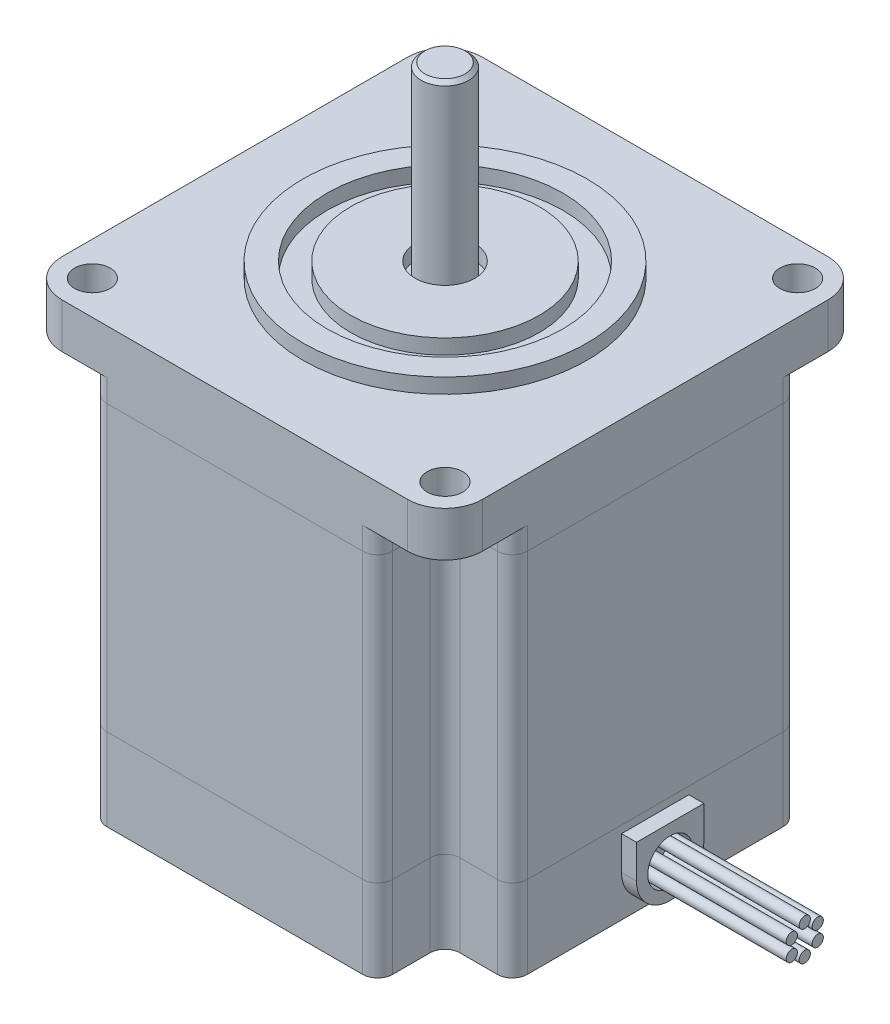
SolidWorks part; units mm, degrees
other "Camera1"
ref_plane "Front Plane" through (0, 0, 0) normal (0, 0, 1) x (1, 0, 0)
ref_plane "Top Plane" through (0, 0, 0) normal (0, 1, 0) x (1, 0, 0)
ref_plane "Right Plane" through (0, 0, 0) normal (1, 0, 0) x (0, 0, -1)
sketch "Sketch1" plane through (0, 0, 0) normal (0, 1, 0) x (1, 0, 0)
  line L1 (28.1, -28.1) -> (-28.1, -28.1)
  line L2 (28.1, -28.1) -> (28.1, 28.1)
  line L3 (28.1, 28.1) -> (-28.1, 28.1)
  line L4 (-28.1, -28.1) -> (-28.1, 28.1)
  line L5 (0, 28.1) -> (0, -28.1) construction
  line L6 (21, 0) -> (-28.1, 0) construction
  circle A0 centre (23.57, 23.57) radius 2.375
  circle A1 centre (23.57, -23.57) radius 2.375
  circle A2 centre (-23.57, -23.57) radius 2.375
  circle A3 centre (-23.57, 23.57) radius 2.375
  point P0 (0, 0)
  point P1 (-28.1, 28.1)
  point P6 (0, 28.1)
  point P7 (-28.1, 0)
  point P15 (0, 0)
  point P19 (0, -28.1)
  dimension "D2" = 4.75
  dimension "D1" = 56.2
  dimension "D4" = 47.14
  dimension "D3" = 4
extrude "Boss-Extrude2" add sketch "Sketch1" along normal blind 11
sketch "Sketch2" plane through (0, 11, 0) normal (0, 1, 0) x (1, 0, 0)
  line L8 (28.1, 28.1) -> (-28.1, 28.1)
  line L10 (-28.1, 28.1) -> (-28.1, -28.1)
  line L12 (-28.1, -28.1) -> (28.1, -28.1)
  line L14 (28.1, -28.1) -> (28.1, 28.1)
  line L16 (28.1, 28.1) -> (-28.1, 28.1)
  line L18 (-28.1, 28.1) -> (-28.1, -28.1)
  line L20 (-28.1, -28.1) -> (28.1, -28.1)
  line L22 (28.1, -28.1) -> (28.1, 28.1)
  circle A0 centre (-23.57, -23.57) radius 2.375 construction
  circle A1 centre (23.57, -23.57) radius 2.375 construction
  circle A2 centre (23.57, 23.57) radius 2.375 construction
  circle A3 centre (-23.57, 23.57) radius 2.375 construction
  circle A4 centre (-23.57, -23.57) radius 2.375
  circle A5 centre (23.57, -23.57) radius 2.375
  circle A6 centre (23.57, 23.57) radius 2.375
  circle A7 centre (-23.57, 23.57) radius 2.375
  dimension "D1" = 0
extrude "Boss-Extrude3" add sketch "Sketch2" along normal blind 38 separate body
sketch "Sketch3" plane through (0, 49, 0) normal (0, 1, 0) x (1, 0, 0)
  line L9 (28.1, 28.1) -> (-28.1, 28.1)
  line L11 (-28.1, 28.1) -> (-28.1, -28.1)
  line L13 (-28.1, -28.1) -> (28.1, -28.1)
  line L15 (28.1, -28.1) -> (28.1, 28.1)
  line L17 (28.1, 28.1) -> (-28.1, 28.1)
  line L19 (-28.1, 28.1) -> (-28.1, -28.1)
  line L21 (-28.1, -28.1) -> (28.1, -28.1)
  line L23 (28.1, -28.1) -> (28.1, 28.1)
  circle A0 centre (23.57, 23.57) radius 2.375 construction
  circle A1 centre (23.57, -23.57) radius 2.375 construction
  circle A2 centre (-23.57, -23.57) radius 2.375 construction
  circle A3 centre (-23.57, 23.57) radius 2.375 construction
  circle A4 centre (23.57, 23.57) radius 2.375
  circle A5 centre (23.57, -23.57) radius 2.375
  circle A6 centre (-23.57, -23.57) radius 2.375
  circle A7 centre (-23.57, 23.57) radius 2.375
  dimension "D1" = 0
extrude "Boss-Extrude4" add sketch "Sketch3" along normal blind 9 separate body
sketch "Sketch4" plane through (28.1, 0, 0) normal (1, 0, 0) x (0, 0, -1)
  line L1 (0, 0) -> (0, 11) construction
  line L2 (-28.1, 11) -> (28.1, 11) construction
  line L3 (-4.5, 5.5) -> (-4.5, 10)
  line L4 (-4.5, 10) -> (4.5, 10)
  line L5 (4.5, 5.5) -> (4.5, 10)
  arc A0 (-4.5, 5.5) -> (4.5, 5.5) centre (0, 5.5) ccw
  circle A1 centre (0, 5.5) radius 3
  point P11 (0, 10)
  dimension "D1" = 6
  dimension "D2" = 9
extrude "Boss-Extrude5" add sketch "Sketch4" along normal blind 2 separate body
sketch "Sketch5" plane through (28.1, 0, 0) normal (1, 0, 0) x (0, 0, -1)
  circle A0 centre (-1.7321, 4.5) radius 0.75
  circle A1 centre (0, 3.5) radius 0.75
  circle A2 centre (-1.7321, 6.5) radius 0.75
  circle A3 centre (0, 7.5) radius 0.75
  circle A4 centre (1.7321, 6.5) radius 0.75
  circle A5 centre (1.7321, 4.5) radius 0.75
  circle A6 centre (0, 5.5) radius 2 construction
  point P15 (0, 5.5)
  dimension "D1" = 1.5
  dimension "D3" = 4
  dimension "D2" = 6
extrude "Boss-Extrude6" add sketch "Sketch5" along normal blind 20 separate body contours A2 | A0 | A1 | A5 | A4 | A3
sketch "Sketch6" plane through (0, 58, 0) normal (0, 1, 0) x (1, 0, 0)
  circle A0 centre (0, 0) radius 12.6
  circle A1 centre (0, 0) radius 19
  circle A2 centre (0, 0) radius 15.75
  circle A3 centre (0, 0) radius 4
  dimension "D1" = 25.2
  dimension "D2" = 38
  dimension "D3" = 31.5
  dimension "D4" = 8
extrude "Boss-Extrude7" add sketch "Sketch6" along normal blind 2 contours A1 A2 | A0 region at (-12.2436, 58, 0) region at (-18.4626, 58, 0)
sketch "Sketch7" plane through (0, 58, 0) normal (0, 1, 0) x (1, 0, 0)
  circle A0 centre (0, 0) radius 3.175
  dimension "D1" = 6.35
extrude "Boss-Extrude8" add sketch "Sketch7" along normal blind 25 separate body
sketch "Sketch8" plane through (0, 83, 0) normal (0, 1, 0) x (1, 0, 0)
  circle A0 centre (0, 0) radius 7.675
  circle A1 centre (0, 0) radius 3.175
  circle A2 centre (0, 0) radius 3.175
  dimension "D2" = 15.35
  dimension "D1" = 0
extrude "Boss-Extrude9" [suppressed] add sketch "Sketch8" against normal blind 10 separate body
sketch "Sketch9" [suppressed] plane through (0, 56, 0) normal (0, -1, 0) x (1, 0, 0)
  circle A0 centre (0, 0) radius 10
  dimension "D1" = 20
extrude "Boss-Extrude10" [suppressed] add sketch "Sketch9" against normal blind 1
sketch "Sketch10" [suppressed] plane through (0, 66, 0) normal (0, 1, 0) x (1, 0, 0)
  line L0 (0, 7.675) -> (0, 8.675) construction
  line L1 (-0.6, 7.6515) -> (-0.3, 8.4658)
  line L2 (0.6, 7.6515) -> (0.3, 8.4658)
  line L3 (1.1177, 7.5932) -> (1.5913, 8.3203)
  line L4 (2.2876, 7.3262) -> (2.1763, 8.1868)
  line L5 (1.7078, 7.4826) -> (1.9304, 8.4575) construction
  line L6 (2.7793, 7.1541) -> (3.4029, 7.7576)
  line L7 (3.8604, 6.6334) -> (3.9435, 7.4973)
  line L8 (3.3301, 6.9149) -> (3.7639, 7.8159) construction
  line L9 (4.3015, 6.3563) -> (5.0438, 6.8059)
  line L10 (5.2397, 5.6081) -> (5.5129, 6.4318)
  line L11 (4.7853, 6.0006) -> (5.4088, 6.7824) construction
  line L12 (5.6081, 5.2397) -> (6.4318, 5.5129)
  line L13 (6.3563, 4.3015) -> (6.8059, 5.0438)
  line L14 (6.0006, 4.7853) -> (6.7824, 5.4088) construction
  line L15 (6.6334, 3.8604) -> (7.4973, 3.9435)
  line L16 (7.1541, 2.7793) -> (7.7576, 3.4029)
  line L17 (6.9149, 3.3301) -> (7.8159, 3.7639) construction
  line L18 (7.3262, 2.2876) -> (8.1868, 2.1763)
  line L19 (7.5932, 1.1177) -> (8.3203, 1.5913)
  line L20 (7.4826, 1.7078) -> (8.4575, 1.9304) construction
  line L21 (7.6515, 0.6) -> (8.4658, 0.3)
  line L22 (7.6515, -0.6) -> (8.4658, -0.3)
  line L23 (7.675, 0) -> (8.675, 0) construction
  line L24 (7.5932, -1.1177) -> (8.3203, -1.5913)
  line L25 (7.3262, -2.2876) -> (8.1868, -2.1763)
  line L26 (7.4826, -1.7078) -> (8.4575, -1.9304) construction
  line L27 (7.1541, -2.7793) -> (7.7576, -3.4029)
  line L28 (6.6334, -3.8604) -> (7.4973, -3.9435)
  line L29 (6.9149, -3.3301) -> (7.8159, -3.7639) construction
  line L30 (6.3563, -4.3015) -> (6.8059, -5.0438)
  line L31 (5.6081, -5.2397) -> (6.4318, -5.5129)
  line L32 (6.0006, -4.7853) -> (6.7824, -5.4088) construction
  line L33 (5.2397, -5.6081) -> (5.5129, -6.4318)
  line L34 (4.3015, -6.3563) -> (5.0438, -6.8059)
  line L35 (4.7853, -6.0006) -> (5.4088, -6.7824) construction
  line L36 (3.8604, -6.6334) -> (3.9435, -7.4973)
  line L37 (2.7793, -7.1541) -> (3.4029, -7.7576)
  line L38 (3.3301, -6.9149) -> (3.7639, -7.8159) construction
  line L39 (2.2876, -7.3262) -> (2.1763, -8.1868)
  line L40 (1.1177, -7.5932) -> (1.5913, -8.3203)
  line L41 (1.7078, -7.4826) -> (1.9304, -8.4575) construction
  line L42 (0.6, -7.6515) -> (0.3, -8.4658)
  line L43 (-0.6, -7.6515) -> (-0.3, -8.4658)
  line L44 (0, -7.675) -> (0, -8.675) construction
  line L45 (-1.1177, -7.5932) -> (-1.5913, -8.3203)
  line L46 (-2.2876, -7.3262) -> (-2.1763, -8.1868)
  line L47 (-1.7078, -7.4826) -> (-1.9304, -8.4575) construction
  line L48 (-2.7793, -7.1541) -> (-3.4029, -7.7576)
  line L49 (-3.8604, -6.6334) -> (-3.9435, -7.4973)
  line L50 (-3.3301, -6.9149) -> (-3.7639, -7.8159) construction
  line L51 (-4.3015, -6.3563) -> (-5.0438, -6.8059)
  line L52 (-5.2397, -5.6081) -> (-5.5129, -6.4318)
  line L53 (-4.7853, -6.0006) -> (-5.4088, -6.7824) construction
  line L54 (-5.6081, -5.2397) -> (-6.4318, -5.5129)
  line L55 (-6.3563, -4.3015) -> (-6.8059, -5.0438)
  line L56 (-6.0006, -4.7853) -> (-6.7824, -5.4088) construction
  line L57 (-6.6334, -3.8604) -> (-7.4973, -3.9435)
  line L58 (-7.1541, -2.7793) -> (-7.7576, -3.4029)
  line L59 (-6.9149, -3.3301) -> (-7.8159, -3.7639) construction
  line L60 (-7.3262, -2.2876) -> (-8.1868, -2.1763)
  line L61 (-7.5932, -1.1177) -> (-8.3203, -1.5913)
  line L62 (-7.4826, -1.7078) -> (-8.4575, -1.9304) construction
  line L63 (-7.6515, -0.6) -> (-8.4658, -0.3)
  line L64 (-7.6515, 0.6) -> (-8.4658, 0.3)
  line L65 (-7.675, 0) -> (-8.675, 0) construction
  line L66 (-7.5932, 1.1177) -> (-8.3203, 1.5913)
  line L67 (-7.3262, 2.2876) -> (-8.1868, 2.1763)
  line L68 (-7.4826, 1.7078) -> (-8.4575, 1.9304) construction
  line L69 (-7.1541, 2.7793) -> (-7.7576, 3.4029)
  line L70 (-6.6334, 3.8604) -> (-7.4973, 3.9435)
  line L71 (-6.9149, 3.3301) -> (-7.8159, 3.7639) construction
  line L72 (-6.3563, 4.3015) -> (-6.8059, 5.0438)
  line L73 (-5.6081, 5.2397) -> (-6.4318, 5.5129)
  line L74 (-6.0006, 4.7853) -> (-6.7824, 5.4088) construction
  line L75 (-5.2397, 5.6081) -> (-5.5129, 6.4318)
  line L76 (-4.3015, 6.3563) -> (-5.0438, 6.8059)
  line L77 (-4.7853, 6.0006) -> (-5.4088, 6.7824) construction
  line L78 (-3.8604, 6.6334) -> (-3.9435, 7.4973)
  line L79 (-2.7793, 7.1541) -> (-3.4029, 7.7576)
  line L80 (-3.3301, 6.9149) -> (-3.7639, 7.8159) construction
  line L81 (-2.2876, 7.3262) -> (-2.1763, 8.1868)
  line L82 (-1.1177, 7.5932) -> (-1.5913, 8.3203)
  line L83 (-1.7078, 7.4826) -> (-1.9304, 8.4575) construction
  circle A0 centre (0, 0) radius 8.675 construction
  circle A1 centre (0, 0) radius 7.675 construction
  circle A2 centre (0, 0) radius 7.675 construction
  arc A3 (-0.3, 8.4658) -> (0, 8.675) centre (0, 8.3553) cw
  circle A4 centre (0, 0) radius 7.675
  arc A5 (0.6, 7.6515) -> (-0.6, 7.6515) centre (0, 0) ccw
  arc A6 (0.3, 8.4658) -> (0, 8.675) centre (0, 8.3553) ccw
  arc A7 (1.5913, 8.3203) -> (1.9304, 8.4575) centre (1.8592, 8.1458) cw
  arc A8 (2.2876, 7.3262) -> (1.1177, 7.5932) centre (0, 0) ccw
  arc A9 (2.1763, 8.1868) -> (1.9304, 8.4575) centre (1.8592, 8.1458) ccw
  arc A10 (3.4029, 7.7576) -> (3.7639, 7.8159) centre (3.6252, 7.5279) cw
  arc A11 (3.8604, 6.6334) -> (2.7793, 7.1541) centre (0, 0) ccw
  arc A12 (3.9435, 7.4973) -> (3.7639, 7.8159) centre (3.6252, 7.5279) ccw
  arc A13 (5.0438, 6.8059) -> (5.4088, 6.7824) centre (5.2094, 6.5324) cw
  arc A14 (5.2397, 5.6081) -> (4.3015, 6.3563) centre (0, 0) ccw
  arc A15 (5.5129, 6.4318) -> (5.4088, 6.7824) centre (5.2094, 6.5324) ccw
  arc A16 (6.4318, 5.5129) -> (6.7824, 5.4088) centre (6.5324, 5.2094) cw
  arc A17 (6.3563, 4.3015) -> (5.6081, 5.2397) centre (0, 0) ccw
  arc A18 (6.8059, 5.0438) -> (6.7824, 5.4088) centre (6.5324, 5.2094) ccw
  arc A19 (7.4973, 3.9435) -> (7.8159, 3.7639) centre (7.5279, 3.6252) cw
  arc A20 (7.1541, 2.7793) -> (6.6334, 3.8604) centre (0, 0) ccw
  arc A21 (7.7576, 3.4029) -> (7.8159, 3.7639) centre (7.5279, 3.6252) ccw
  arc A22 (8.1868, 2.1763) -> (8.4575, 1.9304) centre (8.1458, 1.8592) cw
  arc A23 (7.5932, 1.1177) -> (7.3262, 2.2876) centre (0, 0) ccw
  arc A24 (8.3203, 1.5913) -> (8.4575, 1.9304) centre (8.1458, 1.8592) ccw
  arc A25 (8.4658, 0.3) -> (8.675, 0) centre (8.3553, 0) cw
  arc A26 (7.6515, -0.6) -> (7.6515, 0.6) centre (0, 0) ccw
  arc A27 (8.4658, -0.3) -> (8.675, 0) centre (8.3553, 0) ccw
  arc A28 (8.3203, -1.5913) -> (8.4575, -1.9304) centre (8.1458, -1.8592) cw
  arc A29 (7.3262, -2.2876) -> (7.5932, -1.1177) centre (0, 0) ccw
  arc A30 (8.1868, -2.1763) -> (8.4575, -1.9304) centre (8.1458, -1.8592) ccw
  arc A31 (7.7576, -3.4029) -> (7.8159, -3.7639) centre (7.5279, -3.6252) cw
  arc A32 (6.6334, -3.8604) -> (7.1541, -2.7793) centre (0, 0) ccw
  arc A33 (7.4973, -3.9435) -> (7.8159, -3.7639) centre (7.5279, -3.6252) ccw
  arc A34 (6.8059, -5.0438) -> (6.7824, -5.4088) centre (6.5324, -5.2094) cw
  arc A35 (5.6081, -5.2397) -> (6.3563, -4.3015) centre (0, 0) ccw
  arc A36 (6.4318, -5.5129) -> (6.7824, -5.4088) centre (6.5324, -5.2094) ccw
  arc A37 (5.5129, -6.4318) -> (5.4088, -6.7824) centre (5.2094, -6.5324) cw
  arc A38 (4.3015, -6.3563) -> (5.2397, -5.6081) centre (0, 0) ccw
  arc A39 (5.0438, -6.8059) -> (5.4088, -6.7824) centre (5.2094, -6.5324) ccw
  arc A40 (3.9435, -7.4973) -> (3.7639, -7.8159) centre (3.6252, -7.5279) cw
  arc A41 (2.7793, -7.1541) -> (3.8604, -6.6334) centre (0, 0) ccw
  arc A42 (3.4029, -7.7576) -> (3.7639, -7.8159) centre (3.6252, -7.5279) ccw
  arc A43 (2.1763, -8.1868) -> (1.9304, -8.4575) centre (1.8592, -8.1458) cw
  arc A44 (1.1177, -7.5932) -> (2.2876, -7.3262) centre (0, 0) ccw
  arc A45 (1.5913, -8.3203) -> (1.9304, -8.4575) centre (1.8592, -8.1458) ccw
  arc A46 (0.3, -8.4658) -> (0, -8.675) centre (0, -8.3553) cw
  arc A47 (-0.6, -7.6515) -> (0.6, -7.6515) centre (0, 0) ccw
  arc A48 (-0.3, -8.4658) -> (0, -8.675) centre (0, -8.3553) ccw
  arc A49 (-1.5913, -8.3203) -> (-1.9304, -8.4575) centre (-1.8592, -8.1458) cw
  arc A50 (-2.2876, -7.3262) -> (-1.1177, -7.5932) centre (0, 0) ccw
  arc A51 (-2.1763, -8.1868) -> (-1.9304, -8.4575) centre (-1.8592, -8.1458) ccw
  arc A52 (-3.4029, -7.7576) -> (-3.7639, -7.8159) centre (-3.6252, -7.5279) cw
  arc A53 (-3.8604, -6.6334) -> (-2.7793, -7.1541) centre (0, 0) ccw
  arc A54 (-3.9435, -7.4973) -> (-3.7639, -7.8159) centre (-3.6252, -7.5279) ccw
  arc A55 (-5.0438, -6.8059) -> (-5.4088, -6.7824) centre (-5.2094, -6.5324) cw
  arc A56 (-5.2397, -5.6081) -> (-4.3015, -6.3563) centre (0, 0) ccw
  arc A57 (-5.5129, -6.4318) -> (-5.4088, -6.7824) centre (-5.2094, -6.5324) ccw
  arc A58 (-6.4318, -5.5129) -> (-6.7824, -5.4088) centre (-6.5324, -5.2094) cw
  arc A59 (-6.3563, -4.3015) -> (-5.6081, -5.2397) centre (0, 0) ccw
  arc A60 (-6.8059, -5.0438) -> (-6.7824, -5.4088) centre (-6.5324, -5.2094) ccw
  arc A61 (-7.4973, -3.9435) -> (-7.8159, -3.7639) centre (-7.5279, -3.6252) cw
  arc A62 (-7.1541, -2.7793) -> (-6.6334, -3.8604) centre (0, 0) ccw
  arc A63 (-7.7576, -3.4029) -> (-7.8159, -3.7639) centre (-7.5279, -3.6252) ccw
  arc A64 (-8.1868, -2.1763) -> (-8.4575, -1.9304) centre (-8.1458, -1.8592) cw
  arc A65 (-7.5932, -1.1177) -> (-7.3262, -2.2876) centre (0, 0) ccw
  arc A66 (-8.3203, -1.5913) -> (-8.4575, -1.9304) centre (-8.1458, -1.8592) ccw
  arc A67 (-8.4658, -0.3) -> (-8.675, 0) centre (-8.3553, 0) cw
  arc A68 (-7.6515, 0.6) -> (-7.6515, -0.6) centre (0, 0) ccw
  arc A69 (-8.4658, 0.3) -> (-8.675, 0) centre (-8.3553, 0) ccw
  arc A70 (-8.3203, 1.5913) -> (-8.4575, 1.9304) centre (-8.1458, 1.8592) cw
  arc A71 (-7.3262, 2.2876) -> (-7.5932, 1.1177) centre (0, 0) ccw
  arc A72 (-8.1868, 2.1763) -> (-8.4575, 1.9304) centre (-8.1458, 1.8592) ccw
  arc A73 (-7.7576, 3.4029) -> (-7.8159, 3.7639) centre (-7.5279, 3.6252) cw
  arc A74 (-6.6334, 3.8604) -> (-7.1541, 2.7793) centre (0, 0) ccw
  arc A75 (-7.4973, 3.9435) -> (-7.8159, 3.7639) centre (-7.5279, 3.6252) ccw
  arc A76 (-6.8059, 5.0438) -> (-6.7824, 5.4088) centre (-6.5324, 5.2094) cw
  arc A77 (-5.6081, 5.2397) -> (-6.3563, 4.3015) centre (0, 0) ccw
  arc A78 (-6.4318, 5.5129) -> (-6.7824, 5.4088) centre (-6.5324, 5.2094) ccw
  arc A79 (-5.5129, 6.4318) -> (-5.4088, 6.7824) centre (-5.2094, 6.5324) cw
  arc A80 (-4.3015, 6.3563) -> (-5.2397, 5.6081) centre (0, 0) ccw
  arc A81 (-5.0438, 6.8059) -> (-5.4088, 6.7824) centre (-5.2094, 6.5324) ccw
  arc A82 (-3.9435, 7.4973) -> (-3.7639, 7.8159) centre (-3.6252, 7.5279) cw
  arc A83 (-2.7793, 7.1541) -> (-3.8604, 6.6334) centre (0, 0) ccw
  arc A84 (-3.4029, 7.7576) -> (-3.7639, 7.8159) centre (-3.6252, 7.5279) ccw
  arc A85 (-2.1763, 8.1868) -> (-1.9304, 8.4575) centre (-1.8592, 8.1458) cw
  arc A86 (-1.1177, 7.5932) -> (-2.2876, 7.3262) centre (0, 0) ccw
  arc A87 (-1.5913, 8.3203) -> (-1.9304, 8.4575) centre (-1.8592, 8.1458) ccw
  point P236 (0, 0)
  dimension "D1" = 17.35
  dimension "D2" = 0
  dimension "D3" = 1.2
  dimension "D5" = 0.6
  dimension "D4" = 28
extrude "Boss-Extrude12" [suppressed] add sketch "Sketch10" against normal blind 9
sketch "Sketch11" plane through (0, 0, 0) normal (0, -1, 0) x (1, 0, 0)
  line L0 (0, 21.8817) -> (0, 0) construction
  line L2 (0, 0) -> (43.9252, 0) construction
  line L4 (28.1, 23.6) -> (19.1, 23.6) construction
  line L5 (-28.1, 28.1) -> (-19.1, 28.1)
  line L6 (-28.1, 28.1) -> (-28.1, 19.1)
  line L7 (-28.1, 19.1) -> (-19.1, 19.1)
  line L8 (-19.1, 28.1) -> (-19.1, 19.1)
  line L9 (-23.6, 19.1) -> (-23.6, 28.1) construction
  line L10 (-28.1, 23.6) -> (-19.1, 23.6) construction
  line L11 (23.6, 19.1) -> (23.6, 28.1) construction
  line L12 (19.1, 28.1) -> (19.1, 19.1)
  line L13 (28.1, 19.1) -> (19.1, 19.1)
  line L14 (28.1, 28.1) -> (28.1, 19.1)
  line L15 (28.1, 28.1) -> (19.1, 28.1)
  line L16 (23.6, -19.1) -> (23.6, -28.1) construction
  line L17 (-28.1, -23.6) -> (-19.1, -23.6) construction
  line L18 (-23.6, -19.1) -> (-23.6, -28.1) construction
  line L19 (28.1, -23.6) -> (19.1, -23.6) construction
  line L20 (28.1, -28.1) -> (19.1, -28.1)
  line L21 (28.1, -28.1) -> (28.1, -19.1)
  line L22 (28.1, -19.1) -> (19.1, -19.1)
  line L23 (19.1, -28.1) -> (19.1, -19.1)
  line L24 (-19.1, -28.1) -> (-19.1, -19.1)
  line L25 (-28.1, -19.1) -> (-19.1, -19.1)
  line L26 (-28.1, -28.1) -> (-28.1, -19.1)
  line L27 (-28.1, -28.1) -> (-19.1, -28.1)
  point P20 (23.6, 23.6)
  point P38 (-23.6, -23.6)
  point P39 (23.6, -23.6)
  point P52 (-23.6, 23.6)
  dimension "D1" = 9
extrude "Cut-Extrude1" cut sketch "Sketch11" against normal offset from surface (52 mm away) 6 up to face at (0, 58, 19)
fillet "Fillet1" radius 5 4 edges at (-28.1, 55, 28.1) (28.1, 55, 28.1) (28.1, 55, -28.1) (-28.1, 55, -28.1)
fillet "Fillet2" radius 2 12 edges at (19.1, 5.5, -28.1) (19.1, 5.5, -19.1) (28.1, 5.5, -19.1) (-28.1, 5.5, -19.1) (-19.1, 5.5, -19.1) (-19.1, 5.5, -28.1) (-28.1, 5.5, 19.1) (-19.1, 5.5, 19.1) (-19.1, 5.5, 28.1) (28.1, 5.5, 19.1) (19.1, 5.5, 28.1) (19.1, 5.5, 19.1)
fillet "Fillet3" radius 2 12 edges at (28.1, 30, 19.1) (19.1, 30, 19.1) (19.1, 30, 28.1) (-19.1, 30, 28.1) (-19.1, 30, 19.1) (-28.1, 30, 19.1) (-28.1, 30, -19.1) (-19.1, 30, -19.1) (-19.1, 30, -28.1) (19.1, 30, -28.1) (28.1, 30, -19.1) (19.1, 30, -19.1)
chamfer "Chamfer1" distance 0.5 angle 45 1 edges at (0, 83, 3.175)
fillet "Fillet4" radius 2 12 edges at (19.1, 50.5, -28.1) (28.1, 50.5, -19.1) (19.1, 50.5, -19.1) (-19.1, 50.5, -28.1) (-19.1, 50.5, -19.1) (-28.1, 50.5, -19.1) (-28.1, 50.5, 19.1) (-19.1, 50.5, 19.1) (-19.1, 50.5, 28.1) (28.1, 50.5, 19.1) (19.1, 50.5, 19.1) (19.1, 50.5, 28.1)
